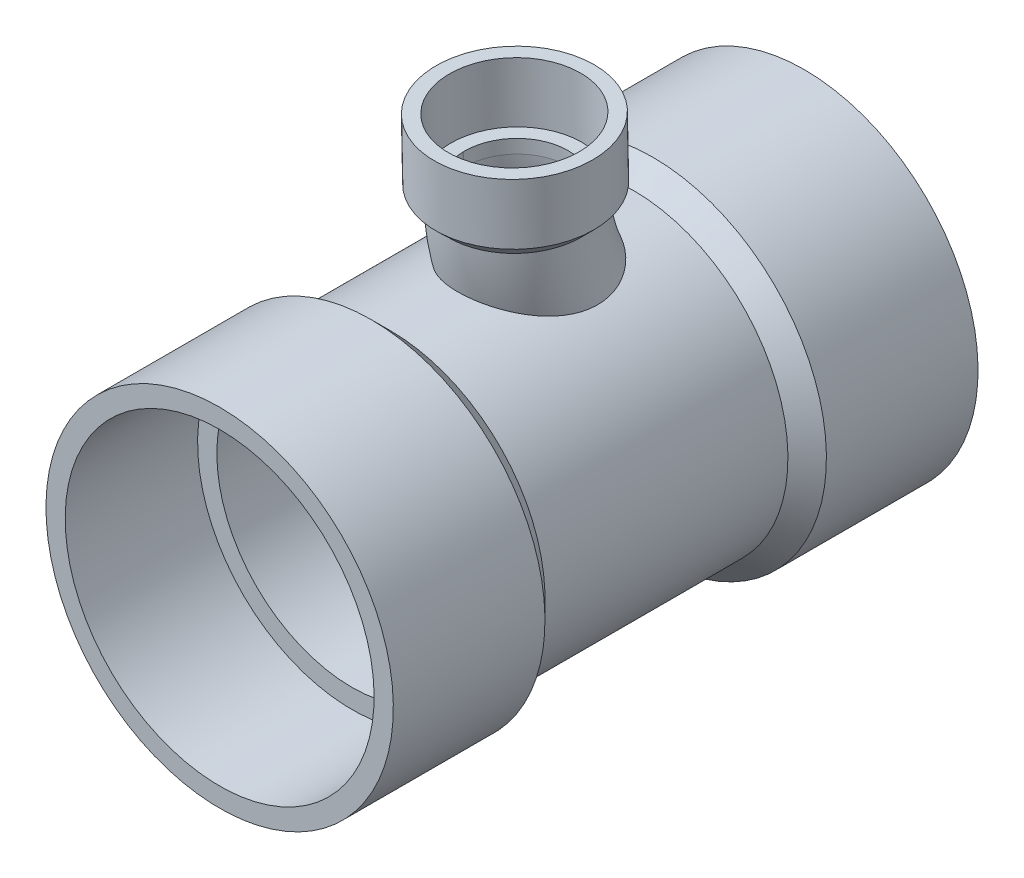
SolidWorks part; units mm, degrees
ref_plane "Front Plane" through (0, 0, 0) normal (0, 0, 1) x (1, 0, 0)
ref_plane "Top Plane" through (0, 0, 0) normal (0, 1, 0) x (1, 0, 0)
ref_plane "Right Plane" through (0, 0, 0) normal (1, 0, 0) x (0, 0, -1)
sketch "RunRoute" plane through (0, 0, 0) normal (0, 0, 1) x (1, 0, 0)
  circle A0 centre (0, 0) radius 44.45
  circle A1 centre (0, 0) radius 38.9128
  dimension "Diameter" = 88.9
  dimension "HubD" = 5.5372
sketch "Sketch2" plane through (0, 0, 0) normal (1, 0, 0) x (0, 0, -1)
  line L0 (0, 0) -> (-1.3301, 63.5) construction
  line L1 (0, 0) -> (-48.4188, 0) construction
  line L2 (0, 0) -> (43.6562, 0) construction
  arc A0 (-1.3301, 63.5) -> (43.6562, 0) centre (68.0302, 64.9529) ccw
  point P8 (0, 0)
  dimension "DimensionC" = 43.6562
  dimension "DimensionB" = 92.075
  dimension "Angle" = 88.8
  dimension "DimensionA" = 63.5
ref_plane "Outlet Plane" through (0, 63.5, 1.3301) normal (0, 0.9998, 0.0209) x (1, 0, 0)
sketch "OutletRoute" plane through (0, 63.5, 1.3301) normal (0, 0.9998, 0.0209) x (1, 0, 0)
  circle A0 centre (0, 0) radius 19.05
  circle A1 centre (0, 0) radius 15.0876
  dimension "OutletHubD" = 3.9624
  dimension "OutletRoute" = 38.1
extrude "Boss-Extrude1" add sketch "RunRoute" along normal up to vertex (48.4188 mm away) and the other way up to vertex (43.6562 mm away) up to point (0, 0, 48.4188) other way up to point (0, 0, -43.6562)
sketch "Sketch6" plane through (0, 0, 0) normal (1, 0, 0) x (0, 0, -1)
  line L0 (17.7157, 63.899) -> (-20.376, 63.101) construction
  line L1 (43.6562, 44.45) -> (-48.4188, 44.45) construction
  line L2 (17.7157, 63.899) -> (17.0887, 93.8332) construction
  line L3 (-20.376, 63.101) -> (-20.9875, 92.2953) construction
  line L4 (43.6562, 44.45) -> (-48.4188, 44.45) construction
  line L6 (13.7542, 63.816) -> (-16.4144, 63.184) construction
  arc A0 (17.7157, 63.899) -> (22.0705, 44.45) centre (68.0302, 64.9529) ccw
  arc A1 (-20.376, 63.101) -> (-17.9856, 44.45) centre (68.0302, 64.9529) ccw
  arc A2 (-16.4144, 63.184) -> (-13.9067, 44.45) centre (68.0302, 64.9529) ccw
  arc A3 (13.7542, 63.816) -> (17.7628, 44.45) centre (68.0302, 64.9529) ccw
  arc A4 (-1.3301, 63.5) -> (43.6562, 0) centre (68.0302, 64.9529) ccw construction
ref_plane "Plane2" through (0, 44.45, 0) normal (0, -1, 0) x (-1, 0, 0)
sweep "Sweep1" add profiles "OutletRoute" path "Sketch2"
sketch "Sketch3" plane through (0, 0, 0) normal (1, 0, 0) x (0, 0, -1)
  line L0 (43.6562, 0) -> (43.6562, -38.9128) construction
  line L1 (43.6562, -44.45) -> (81.7563, -44.45)
  line L2 (81.7563, -44.45) -> (81.7563, -49.9872)
  line L3 (81.7563, -49.9872) -> (38.1191, -49.9872)
  line L4 (38.1191, -49.9872) -> (32.5819, -44.45)
  line L5 (32.5819, -44.45) -> (32.5819, -38.9128)
  line L6 (32.5819, -38.9128) -> (43.6562, -38.9128)
  line L7 (43.6562, -38.9128) -> (43.6562, -44.45)
  line L8 (0, 0) -> (43.6562, 0) construction
  line L11 (43.6562, 0) -> (81.7562, 0) construction
  line L12 (81.7562, 0) -> (81.7563, -44.45) construction
  line L13 (-48.4188, -44.45) -> (43.6562, -44.45) construction
  line L14 (-48.4188, 0) -> (-86.5187, 0) construction
  line L15 (-86.5187, 0) -> (-86.5187, -44.45) construction
  line L16 (-86.5187, -44.45) -> (-86.5187, -49.9872)
  line L17 (-86.5187, -49.9872) -> (-42.8815, -49.9872)
  line L18 (-42.8815, -49.9872) -> (-37.3443, -44.45)
  line L19 (-37.3443, -44.45) -> (-37.3443, -38.9128)
  line L20 (-37.3443, -38.9128) -> (-48.4188, -38.9128)
  line L21 (-48.4188, -38.9128) -> (-48.4187, -44.45)
  line L22 (-48.4187, -44.45) -> (-86.5187, -44.45)
  line L25 (17.3502, 81.3449) -> (21.3118, 81.4279)
  line L26 (-1.3301, 63.5) -> (-1.6956, 80.946) construction
  line L27 (0, 0) -> (-1.3301, 63.5) construction
  line L28 (-1.6956, 80.946) -> (17.3502, 81.3449) construction
  line L29 (21.3118, 81.4279) -> (21.6805, 63.8257)
  line L30 (17.3502, 81.3449) -> (17.7157, 63.899)
  line L31 (21.6805, 63.8257) -> (17.9549, 59.9407)
  line L32 (17.9549, 59.9407) -> (13.8371, 59.8544)
  line L33 (13.8371, 59.8544) -> (13.7542, 63.816)
  line L34 (13.7542, 63.816) -> (17.7157, 63.899)
  arc A0 (17.7157, 63.899) -> (22.0705, 44.45) centre (68.0302, 64.9529) ccw construction
  dimension "HubC" = 38.1
  dimension "D1" = 5.5372
  dimension "D2" = 88.9
  dimension "D3" = 45
  dimension "D4" = 5.5372
  dimension "D5" = 45
  dimension "D6" = 5.5372
  dimension "D7" = 45
  dimension "OutletHubC" = 17.4498
  dimension "OutletHubD" = 3.9624
  dimension "D8" = 38.1
  dimension "D9" = 3.9624
extrude "Cut-Extrude1" cut sketch "RunRoute<2>" against normal through all both and the other way through all contours A1 region at (0, 0, 0)
sketch "RunRoute<2>" plane through (0, 0, 0) normal (0, 0, 1) x (1, 0, 0) same geometry as "RunRoute"
revolve "Revolve1" add sketch "Sketch3" angle 360 about L26 region at (0, 69.9322, -18.8487)
revolve "Revolve2" add sketch "Sketch3<5>" angle 360 about L14 region at (0, -46.1073, -54.5942) region at (0, -46.1073, 59.3567)
sketch "Sketch3<5>" plane through (0, 0, 0) normal (1, 0, 0) x (0, 0, -1) same geometry as "Sketch3"
ref_plane "Plane3" through (0, 0, 48.4188) normal (0, 0, 1) x (1, 0, 0)
ref_plane "Plane4" through (0, 0, -43.6562) normal (0, 0, -1) x (-1, 0, 0)
other "CPoint1" parameters "Diameter"=76.2, "StubLength"=19.05
ref_axis "Axis1" through (0, 0, 58.4188) along (0, 0, -1)
other "CPoint2" parameters "Diameter"=76.2, "StubLength"=0
ref_axis "Axis2" through (0, 0, -53.6562) along (0, 0, 1)
other "CPoint3" parameters "Diameter"=38.1, "StubLength"=152.4
ref_axis "Axis3" through (0, 73.4978, 1.5396) along (0, -0.9998, -0.0209)
other "RPoint1"
equation "\"D1@Sketch3\"=\"HubD@RunRoute\""
equation "\"D4@Sketch3\"=\"D1@Sketch3\""
equation "\"D6@Sketch3\"=\"D4@Sketch3\""
equation "\"D9@Sketch3\"=\"OutletHubD@Sketch3\""
equation "\"D8@Sketch3\"=\"OutletRoute@OutletRoute\""
equation "\"D2@Sketch3\"=\"Diameter@RunRoute\""
